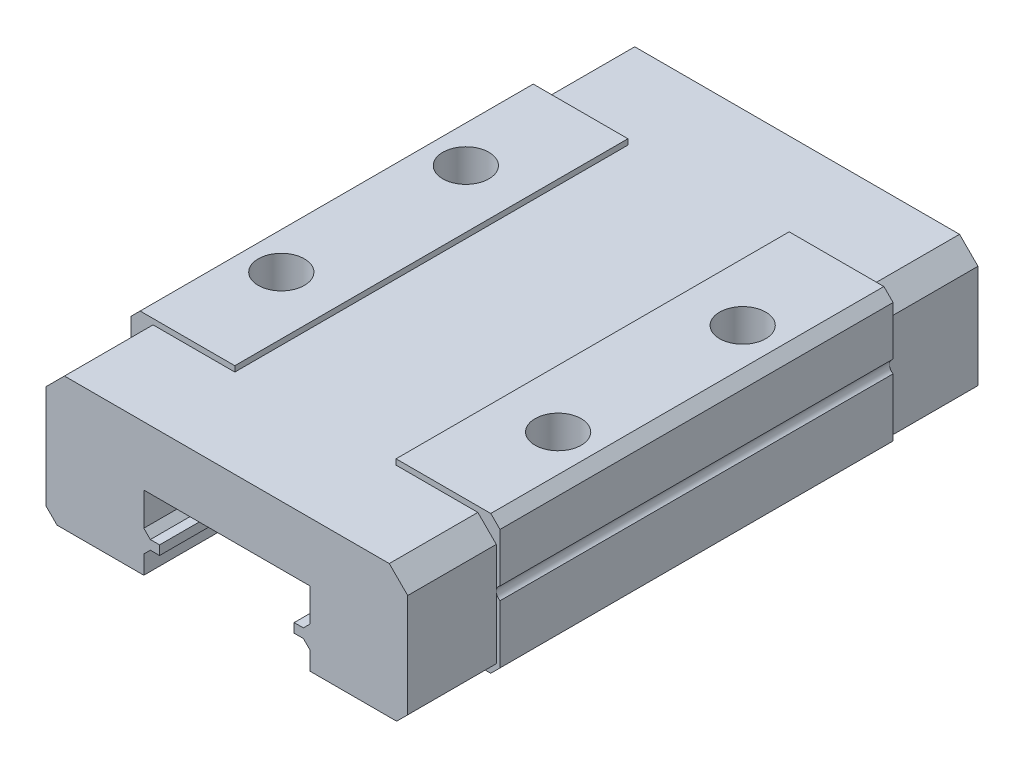
SolidWorks part; units mm, degrees
material "AISI 1020 钢，冷轧"
ref_plane "前视基准面" through (0, 0, 0) normal (0, 0, 1) x (1, 0, 0)
ref_plane "上视基准面" through (0, 0, 0) normal (0, 1, 0) x (1, 0, 0)
ref_plane "右视基准面" through (0, 0, 0) normal (1, 0, 0) x (0, 0, -1)
sketch "草图1" plane through (0, 0, 0) normal (0, 0, 1) x (1, 0, 0)
  line L0 (0, 0) -> (0, 18.7331) construction
  line L1 (-10, 0) -> (-10, 7.5)
  line L2 (4.5, 0) -> (4.5, 1)
  line L3 (4.5, 1) -> (4.1464, 1.3536)
  line L4 (4.1464, 1.3536) -> (3.6464, 1.3536)
  line L5 (3.6464, 1.3536) -> (3.6464, 1.8536)
  line L6 (3.6464, 1.8536) -> (4.1464, 1.8536)
  line L7 (4.1464, 1.8536) -> (4.5, 2.2071)
  line L8 (4.5, 2.2071) -> (4.5, 4)
  line L9 (4.5, 4) -> (-4.5, 4)
  line L10 (4.5, 0) -> (10, 0)
  line L11 (10, 0) -> (10, 7.5)
  line L12 (10, 7.5) -> (-10, 7.5)
  line L13 (-4.5, 0) -> (-10, 0)
  line L14 (-4.5, 2.2071) -> (-4.5, 4)
  line L15 (-4.1464, 1.8536) -> (-4.5, 2.2071)
  line L16 (-3.6464, 1.8536) -> (-4.1464, 1.8536)
  line L17 (-3.6464, 1.3536) -> (-3.6464, 1.8536)
  line L18 (-4.1464, 1.3536) -> (-3.6464, 1.3536)
  line L19 (-4.5, 1) -> (-4.1464, 1.3536)
  line L20 (-4.5, 0) -> (-4.5, 1)
  point P16 (0, 7.5)
  point P19 (0, 4)
  dimension "D1" = 4.5
  dimension "D2" = 1
  dimension "D3" = 0.5
  dimension "D4" = 0.5
  dimension "D5" = 0.5
  dimension "D6" = 4
  dimension "D7" = 10
  dimension "D8" = 7.5
extrude "凸台-拉伸1" add sketch "草图1" against normal blind 30.9
sketch "草图2" plane through (0, 7.5, 0) normal (0, 1, 0) x (1, 0, 0)
  line L0 (0, 30.9) -> (0, 0) construction
  line L1 (10, 30.9) -> (-10, 30.9) construction
  line L2 (10, 15.45) -> (-10, 15.45) construction
  line L3 (10, 30.9) -> (10, 0) construction
  line L4 (-10, 30.9) -> (-10, 0) construction
hole_wizard "M3 螺纹孔1" positions "草图4" profile "草图3" tap size "M3" standard "Gb"
sketch "草图4" plane through (0, 7.5, 0) normal (0, 1, 0) x (1, 0, 0)
  line L0 (0, 30.9) -> (0, 0) construction
  line L1 (10, 15.45) -> (-10, 15.45) construction
  point P0 (7.5, 20.45)
  dimension "D1" = 7.5
  dimension "D2" = 5
sketch "草图3" plane through (7.5, 7.5, -20.45) normal (1, 0, 0) x (0, 0, 1)
  line L0 (0, 0) -> (0, 3.7511)
  line L1 (0, 3.7511) -> (1.25, 3)
  line L2 (1.25, 3) -> (1.25, 0)
  line L5 (1.25, 0) -> (0, 0)
  line L10 (0, 3.7511) -> (-1.25, 3) construction
  line L11 (0, -6.35) -> (0, 107.95) construction
  dimension "螺纹孔钻头直径" = 2.5
  dimension "螺纹孔钻头深度" = 3
  dimension "导头角度" = 118
cosmetic thread "孔螺蚊线1" parameters "D1"=3, "D2"=3
ref_plane "基准面1" through (0, 0, -15.45) normal (0, 0, -1) x (-1, 0, 0)
ref_plane "基准面2" through (0, 0, 0) normal (-1, 0, 0) x (0, 0, 1)
mirror "镜向1" about plane through (0, 0, -15.45) normal (0, 0, -1) of "M3 螺纹孔1"
mirror "镜向2" about plane through (0, 0, 0) normal (-1, 0, 0) of "镜向1", "M3 螺纹孔1"
chamfer "倒角1" distance 0.5 angle 45 2 edges at (10, 7.5, -15.45) (-10, 7.5, -15.45)
sketch "草图5" plane through (0, 7.5, 0) normal (0, 1, 0) x (1, 0, 0)
  line L0 (-9.5, 26.1) -> (-4.3686, 26.1)
  line L1 (-9.5, 30.9) -> (-9.5, 0) construction
  line L2 (-4.3686, 26.1) -> (-4.3686, 4.8)
  line L3 (-4.3686, 4.8) -> (-9.5, 4.8)
  line L4 (0, 30.9) -> (0, -1.0585) construction
  line L5 (9.5, 30.9) -> (-9.5, 30.9) construction
  line L6 (4.3686, 4.8) -> (9.5, 4.8)
  line L7 (4.3686, 26.1) -> (4.3686, 4.8)
  line L8 (9.5, 26.1) -> (4.3686, 26.1)
  line L9 (9.5, 0) -> (-9.5, 0) construction
  line L10 (-9.5, 26.1) -> (-10, 26.1)
  line L11 (-10, 0) -> (-10, 30.9) construction
  line L12 (-10, 26.1) -> (-10, 30.9)
  line L13 (-10, 30.9) -> (10, 30.9)
  line L14 (10, 30.9) -> (10, 26.1)
  line L15 (10, 30.9) -> (10, 0) construction
  line L16 (10, 26.1) -> (9.5, 26.1)
  line L17 (9.5, 4.8) -> (10, 4.8)
  line L18 (10, 4.8) -> (10, 0)
  line L19 (10, 0) -> (-10, 0)
  line L20 (-10, 0) -> (-10, 4.8)
  line L21 (-10, 4.8) -> (-9.5, 4.8)
  dimension "D1" = 4.8
  dimension "D2" = 4.8
extrude "切除-拉伸1" cut sketch "草图5" against normal blind 0.3
sketch "草图6" plane through (0, 7.2, 0) normal (0, 1, 0) x (1, 0, 0)
  line L0 (-10, 30.9) -> (-9.8, 30.9)
  line L1 (9.8, 30.9) -> (-9.8, 30.9) construction
  line L2 (-9.8, 30.9) -> (-9.8, 26.1)
  line L3 (-9.8, 26.1) -> (-10, 26.1)
  line L4 (-10, 0) -> (-10, 30.9) construction
  line L5 (-10, 26.1) -> (-10, 30.9)
  line L6 (0, 30.9) -> (0, 0) construction
  line L7 (-10, 15.45) -> (10, 15.45) construction
  line L8 (10, 30.9) -> (10, 0) construction
  line L9 (10, 26.1) -> (10, 30.9)
  line L10 (9.8, 26.1) -> (10, 26.1)
  line L11 (9.8, 30.9) -> (9.8, 26.1)
  line L12 (10, 30.9) -> (9.8, 30.9)
  line L13 (10, 0) -> (9.8, 0)
  line L14 (9.8, 0) -> (9.8, 4.8)
  line L15 (9.8, 4.8) -> (10, 4.8)
  line L16 (10, 4.8) -> (10, 0)
  line L17 (-10, 4.8) -> (-10, 0)
  line L18 (-9.8, 4.8) -> (-10, 4.8)
  line L19 (-9.8, 0) -> (-9.8, 4.8)
  line L20 (-10, 0) -> (-9.8, 0)
extrude "切除-拉伸2" cut sketch "草图6" against normal blind 8.3
chamfer "倒角2" distance 1 angle 45 4 edges at (-9.8, 7.2, -28.5) (9.8, 7.2, -28.5) (9.8, 7.2, -2.4) (-9.8, 7.2, -2.4)
chamfer "倒角3" distance 0.6 angle 45 4 edges at (9.8, 0, -2.4) (-9.8, 0, -2.4) (-9.8, 0, -28.5) (9.8, 0, -28.5)
chamfer "倒角4" distance 0.5 angle 45 2 edges at (10, 0, -15.45) (-10, 0, -15.45)
sketch "草图7" plane through (0, 0, -26.1) normal (0, 0, -1) x (-1, 0, 0)
  line L0 (-9.8, 0.6) -> (-9.8, 6.2) construction
  line L1 (-4.5, 0) -> (-9.2, 0) construction
  circle A0 centre (-10.2, 4) radius 0.4
  dimension "D1" = 0.8
  dimension "D2" = 0.4
  dimension "D3" = 4
extrude "切除-拉伸3" cut sketch "草图7" against normal up to surface (21.3 mm away) up to face at (8.6488, 4.6273, -4.8)
